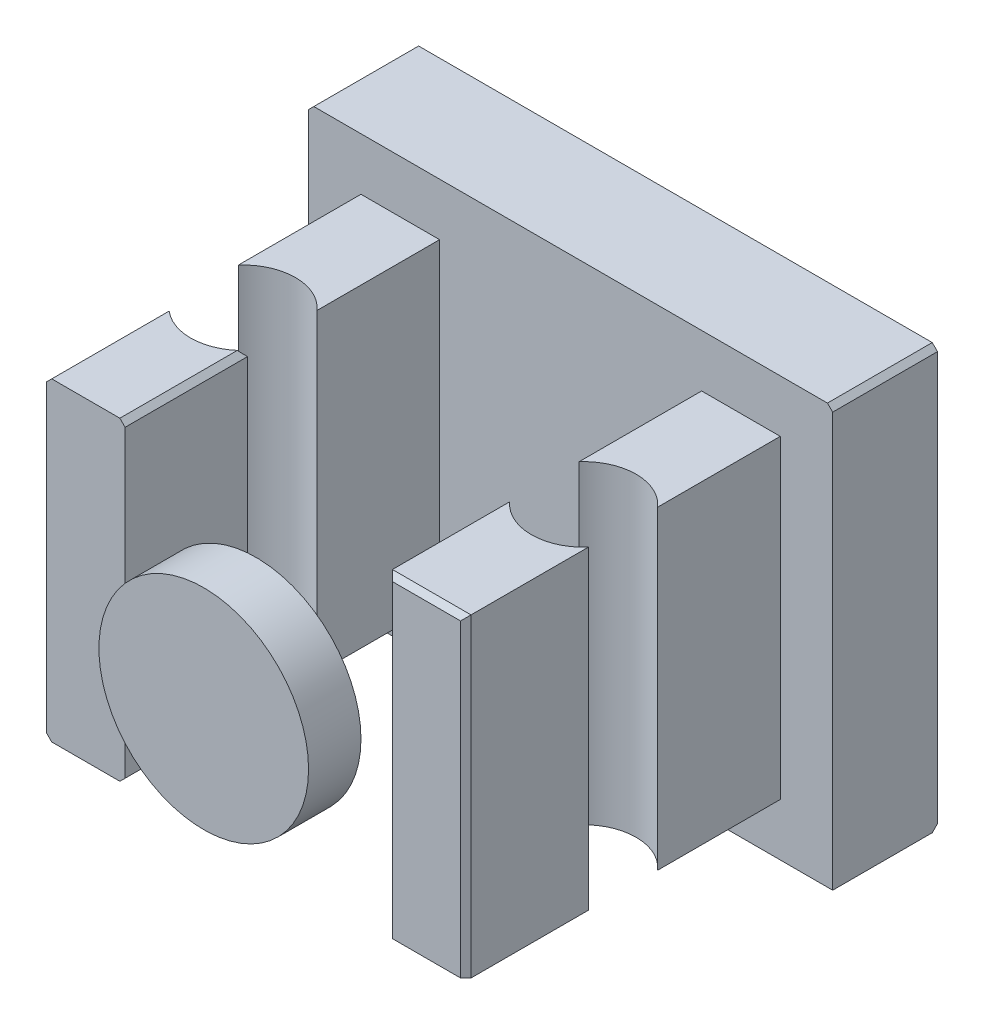
SolidWorks part; units mm, degrees
ref_plane "前视基准面" through (0, 0, 0) normal (0, 0, 1) x (1, 0, 0)
ref_plane "上视基准面" through (0, 0, 0) normal (0, 1, 0) x (1, 0, 0)
ref_plane "右视基准面" through (0, 0, 0) normal (1, 0, 0) x (0, 0, -1)
other "Configuration Table"
sketch "Sketch1" plane through (0, 0, 0) normal (0, 0, 1) x (1, 0, 0)
  line L1 (-50, -40) -> (50, -40)
  line L2 (-50, -40) -> (-50, 40)
  line L3 (-50, 40) -> (50, 40)
  line L4 (50, -40) -> (50, 40)
  line L5 (-50, -40) -> (50, 40) construction
  line L6 (-50, 40) -> (50, -40) construction
  point P0 (0, 0)
extrude "Boss-Extrude1" add sketch "Sketch1" along normal blind 20
ref_plane "Plane1" through (0, 0, 20) normal (0, 0, 1) x (1, 0, 0)
sketch "Sketch2" plane through (0, 0, 20) normal (0, 0, 1) x (1, 0, 0)
  line L1 (-40, -30) -> (-25, -30)
  line L2 (-40, -30) -> (-40, 30)
  line L3 (-40, 30) -> (-25, 30)
  line L4 (-25, -30) -> (-25, 30)
  line L5 (-40, -30) -> (-25, 30) construction
  line L6 (-40, 30) -> (-25, -30) construction
  line L7 (25, -30) -> (40, -30)
  line L8 (25, -30) -> (25, 30)
  line L9 (25, 30) -> (40, 30)
  line L10 (40, -30) -> (40, 30)
  line L11 (25, -30) -> (40, 30) construction
  line L12 (25, 30) -> (40, -30) construction
  point P0 (-32.5, 0)
  point P5 (32.5, 0)
extrude "Boss-Extrude2" add sketch "Sketch2" along normal blind 60
sketch "Sketch3" plane through (0, 0, 0) normal (0, 1, 0) x (1, 0, 0)
  circle A0 centre (-32.5, -50) radius 10
  circle A1 centre (32.5, -50) radius 10
extrude "Cut-Extrude1" cut sketch "Sketch3" along normal blind 100 and the other way blind 100
ref_plane "Plane2" through (0, 0, 80) normal (0, 0, 1) x (1, 0, 0)
sketch "Sketch4" plane through (0, 0, 80) normal (0, 0, 1) x (1, 0, 0)
  circle A0 centre (0, 0) radius 20
extrude "Boss-Extrude3" add sketch "Sketch4" along normal blind 10
ref_plane "Plane3" through (0, 0, 90) normal (0, 0, 1) x (1, 0, 0)
sketch "Sketch5" plane through (0, 0, 90) normal (0, 0, 1) x (1, 0, 0)
  circle A0 centre (0, 0) radius 10
chamfer "Chamfer1" distance 1 angle 45 4 edges at (0, -40, 0) (-50, -40, 10) (-50, 40, 10) (50, 40, 10)
chamfer "Chamfer2" distance 1 angle 45 4 edges at (-40, -30, 68.3072) (-25, -30, 68.3072) (-25, 30, 68.3072) (-40, 30, 68.3072)
chamfer "Chamfer3" distance 1 angle 45 3 edges at (25, 0, 80) (40, 0, 80) (32.5, 30, 80)
ref_plane "bottom_mount_face" through (0, 0, 0) normal (0, 0, 1) x (1, 0, 0)
ref_plane "top_wrist_mount_face" through (0, 0, 90) normal (0, 0, 1) x (1, 0, 0)
sketch3d "3DSketch1"
  line L0 (0, 0, 0) -> (0, 0, 100) construction
ref_axis "mount_axis_z" through (0, 0, 0) along (0, 0, 1)
sketch3d "3DSketch2"
  line L0 (0, -100, 50) -> (0, 100, 50) construction
ref_axis "hinge_axis_y" through (0, -100, 50) along (0, 1, 0)
sketch3d "3DSketch3"
  line L0 (0, 0, 90) -> (0, 0, 190) construction
ref_axis "wrist_gripper_axis_z" through (0, 0, 90) along (0, 0, 1)
